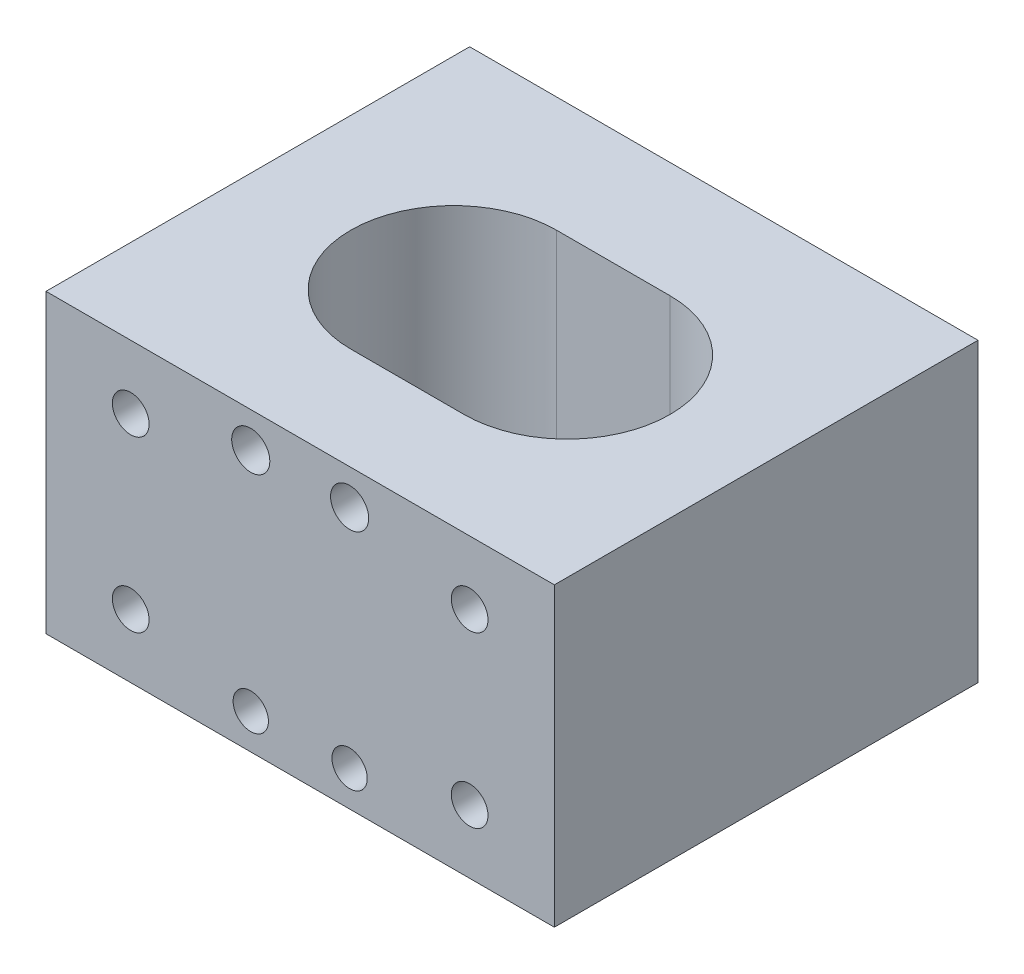
SolidWorks part; units mm, degrees
ref_plane "정면" through (0, 0, 0) normal (0, 0, 1) x (1, 0, 0)
ref_plane "윗면" through (0, 0, 0) normal (0, 1, 0) x (1, 0, 0)
ref_plane "우측면" through (0, 0, 0) normal (1, 0, 0) x (0, 0, -1)
sketch "스케치1" plane through (0, 0, 0) normal (0, 0, 1) x (1, 0, 0)
  line L0 (0, 10.5) -> (0, -10.5) construction
  line L1 (18, -10.5) -> (-18, -10.5)
  line L2 (18, -10.5) -> (18, 10.5)
  line L3 (18, 10.5) -> (-18, 10.5)
  line L4 (-18, -10.5) -> (-18, 10.5)
  line L5 (18, -10.5) -> (-18, 10.5) construction
  line L6 (18, 10.5) -> (-18, -10.5) construction
  line L7 (18, 0) -> (-18, 0) construction
  circle A0 centre (12, 6) radius 1.3
  circle A1 centre (-12, 6) radius 1.3
  circle A2 centre (12, -6) radius 1.3
  circle A3 centre (-12, -6) radius 1.3
  circle A4 centre (3.5, -8) radius 1.25
  circle A5 centre (-3.5, -8) radius 1.25
  circle A6 centre (3.5, 8) radius 1.35
  circle A7 centre (-3.5, 8) radius 1.35
  point P1 (0, 0)
extrude "보스-돌출1" add sketch "스케치1" along normal blind 30 contours A0 | A6 | A7 | A1 | A3 | A5 | A4 | A2 | L4 L1 L2 L3 A5 A4 A1 A0 A2 A3 A6 A7 region at (0, -0.0183, 0) region at (12, 6, 0) region at (-12, 6, 0) region at (12, -6, 0) region at (-12, -6, 0) region at (3.5, -8, 0) region at (-3.5, -8, 0) region at (3.5, 8, 0) region at (-3.5, 8, 0)
extrude "컷-돌출1" cut sketch "스케치1<5>" along normal blind 4 contours A0 | A6 | A7 | A1 | A3 | A5 | A4 | A2 region at (12, 6, 0) region at (-12, 6, 0) region at (-12, -6, 0) region at (3.5, 8, 0) region at (-3.5, 8, 0)
sketch "스케치1<5>" plane through (0, 0, 0) normal (0, 0, 1) x (1, 0, 0) same geometry as "스케치1"
extrude "컷-돌출2" cut sketch "스케치1<6>" against normal blind 4 from surface contours A6 | A0 | A7 | A1 | A3 | A5 | A4 | A2 region at (12, 6, 0) region at (-12, 6, 0) region at (12, -6, 0) region at (-12, -6, 0) region at (3.5, -8, 0) region at (-3.5, -8, 0) region at (3.5, 8, 0) region at (-3.5, 8, 0) starting at face at (0, 0, 30)
sketch "스케치1<6>" plane through (0, 0, 0) normal (0, 0, 1) x (1, 0, 0) same geometry as "스케치1"
sketch "Sketch2" plane through (0, 10.5, 0) normal (0, 1, 0) x (1, 0, 0)
  line L0 (-3.6719, -15.4613) -> (4.3606, -15.4613) construction
  line L1 (-3.6719, -8.1723) -> (4.3606, -8.1723)
  line L2 (-3.6719, -22.7503) -> (4.3606, -22.7503)
  arc A0 (-3.6719, -8.1723) -> (-3.6719, -22.7503) centre (-3.6719, -15.4613) ccw
  arc A1 (4.3606, -22.7503) -> (4.3606, -8.1723) centre (4.3606, -15.4613) ccw
  point P2 (0.3443, -15.4613)
extrude "Cut-Extrude1" cut sketch "Sketch2" against normal blind 30 contours L2 A1 L1 A0
